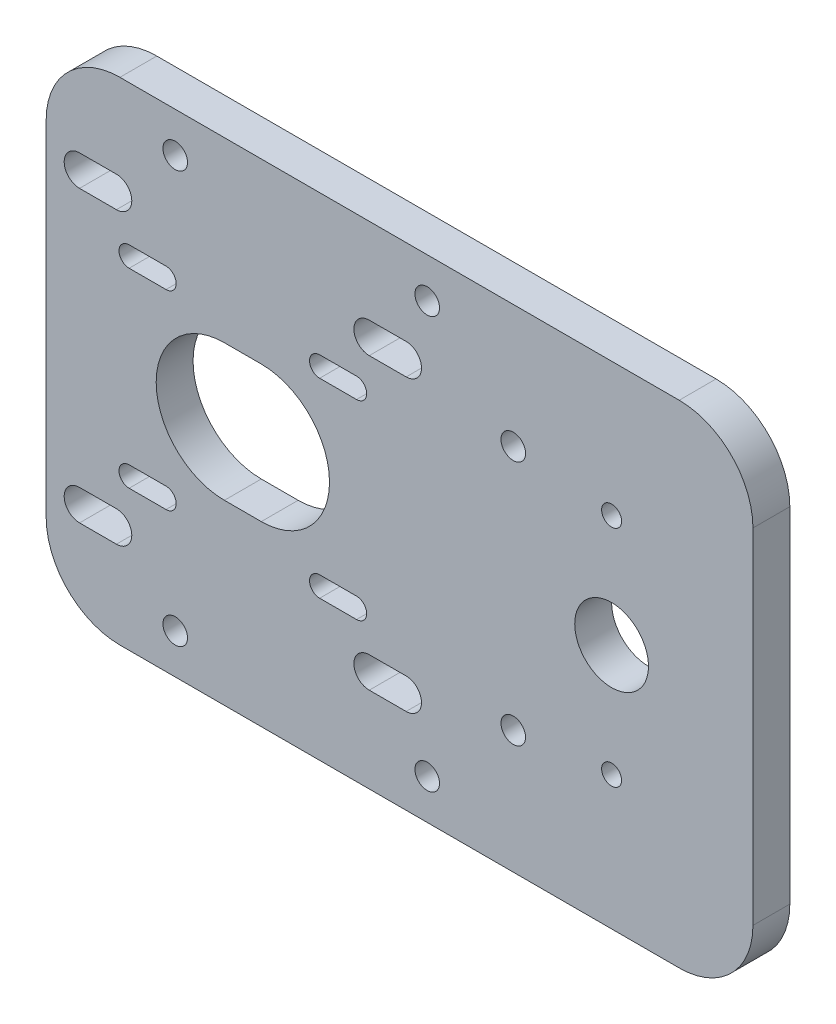
SolidWorks part; units mm, degrees
ref_plane "Alzado" through (0, 0, 0) normal (0, 0, 1) x (1, 0, 0)
ref_plane "Planta" through (0, 0, 0) normal (0, 1, 0) x (1, 0, 0)
ref_plane "Vista lateral" through (0, 0, 0) normal (1, 0, 0) x (0, 0, -1)
sketch "Croquis1" plane through (0, 0, 0) normal (0, 0, 1) x (1, 0, 0)
  line L1 (0, 0) -> (115, 0)
  line L2 (0, 0) -> (0, 80)
  line L3 (0, 80) -> (115, 80)
  line L4 (115, 0) -> (115, 80)
  dimension "D1" = 80
  dimension "D2" = 115
extrude "Saliente-Extruir1" add sketch "Croquis1" along normal blind 6
sketch "Croquis2" plane through (0, 0, 0) normal (0, 0, -1) x (-1, 0, 0)
  line L0 (0, 80) -> (0, 0) construction
  line L1 (0, 40) -> (-115, 40) construction
  line L4 (-115, 0) -> (-115, 80) construction
  line L7 (-29, 40) -> (-35, 40) construction
  line L10 (-29, 28.9) -> (-35, 28.9)
  line L19 (-29, 51.1) -> (-35, 51.1)
  line L20 (-13.5, 24.5) -> (-19.5, 24.5) construction
  line L21 (-13.5, 22.85) -> (-19.5, 22.85)
  line L22 (-13.5, 26.15) -> (-19.5, 26.15)
  line L23 (-44.5, 55.5) -> (-50.5, 55.5) construction
  line L24 (-44.5, 53.85) -> (-50.5, 53.85)
  line L25 (-44.5, 57.15) -> (-50.5, 57.15)
  line L26 (-44.5, 24.5) -> (-50.5, 24.5) construction
  line L27 (-44.5, 22.85) -> (-50.5, 22.85)
  line L28 (-44.5, 26.15) -> (-50.5, 26.15)
  line L29 (-13.5, 55.5) -> (-19.5, 55.5) construction
  line L30 (-13.5, 53.85) -> (-19.5, 53.85)
  line L31 (-13.5, 57.15) -> (-19.5, 57.15)
  line L32 (-92, 0) -> (-92, 80) construction
  line L33 (0, 0) -> (-115, 0) construction
  line L34 (-115, 80) -> (0, 80) construction
  line L35 (-61, 0) -> (-61, 80) construction
  line L36 (-52.57, 16.43) -> (-58.57, 16.43) construction
  line L37 (-52.57, 13.93) -> (-58.57, 13.93)
  line L38 (-52.57, 18.93) -> (-58.57, 18.93)
  line L39 (-5.43, 16.43) -> (-11.43, 16.43) construction
  line L40 (-5.43, 13.93) -> (-11.43, 13.93)
  line L41 (-5.43, 18.93) -> (-11.43, 18.93)
  line L42 (-52.57, 63.57) -> (-58.57, 63.57) construction
  line L43 (-52.57, 61.07) -> (-58.57, 61.07)
  line L44 (-52.57, 66.07) -> (-58.57, 66.07)
  line L45 (-5.43, 63.57) -> (-11.43, 63.57) construction
  line L46 (-5.43, 61.07) -> (-11.43, 61.07)
  line L47 (-5.43, 66.07) -> (-11.43, 66.07)
  circle A5 centre (-92, 40) radius 6
  circle A15 centre (-92, 21.75) radius 1.625
  circle A16 centre (-92, 58.25) radius 1.625
  arc A19 (-29, 28.9) -> (-29, 51.1) centre (-29, 40) ccw
  arc A20 (-35, 51.1) -> (-35, 28.9) centre (-35, 40) ccw
  arc A21 (-13.5, 22.85) -> (-13.5, 26.15) centre (-13.5, 24.5) ccw
  arc A22 (-19.5, 26.15) -> (-19.5, 22.85) centre (-19.5, 24.5) ccw
  arc A23 (-44.5, 53.85) -> (-44.5, 57.15) centre (-44.5, 55.5) ccw
  arc A24 (-50.5, 57.15) -> (-50.5, 53.85) centre (-50.5, 55.5) ccw
  arc A25 (-44.5, 22.85) -> (-44.5, 26.15) centre (-44.5, 24.5) ccw
  arc A26 (-50.5, 26.15) -> (-50.5, 22.85) centre (-50.5, 24.5) ccw
  arc A27 (-13.5, 53.85) -> (-13.5, 57.15) centre (-13.5, 55.5) ccw
  arc A28 (-19.5, 57.15) -> (-19.5, 53.85) centre (-19.5, 55.5) ccw
  arc A29 (-52.57, 13.93) -> (-52.57, 18.93) centre (-52.57, 16.43) ccw
  arc A30 (-58.57, 18.93) -> (-58.57, 13.93) centre (-58.57, 16.43) ccw
  arc A31 (-5.43, 13.93) -> (-5.43, 18.93) centre (-5.43, 16.43) ccw
  arc A32 (-11.43, 18.93) -> (-11.43, 13.93) centre (-11.43, 16.43) ccw
  arc A33 (-52.57, 61.07) -> (-52.57, 66.07) centre (-52.57, 63.57) ccw
  arc A34 (-58.57, 66.07) -> (-58.57, 61.07) centre (-58.57, 63.57) ccw
  arc A35 (-5.43, 61.07) -> (-5.43, 66.07) centre (-5.43, 63.57) ccw
  arc A36 (-11.43, 66.07) -> (-11.43, 61.07) centre (-11.43, 63.57) ccw
  circle A37 centre (-76, 20) radius 2
  circle A38 centre (-76, 60) radius 2
  point P6 (-32, 40)
  point P19 (-16.5, 24.5)
  point P28 (-47.5, 55.5)
  point P35 (-47.5, 24.5)
  point P41 (-55.57, 16.43)
  point P48 (-16.5, 55.5)
  point P63 (-8.43, 16.43)
  point P72 (-55.57, 63.57)
  point P79 (-8.43, 63.57)
  dimension "D2" = 6
  dimension "D3" = 11.1
  dimension "D4" = 3.3
  dimension "D5" = 6
  dimension "D6" = 12
  dimension "D13" = 3.25
  dimension "D14" = 3.25
  dimension "D29" = 2.5
  dimension "D32" = 2.5
  dimension "D34" = 2.5
  dimension "D36" = 2.5
  dimension "D45" = 4
  dimension "D46" = 4
  dimension "D7" = 15.5
  dimension "D8" = 15.5
  dimension "D9" = 3.3
  dimension "D10" = 6
  dimension "D11" = 23
  dimension "D12" = 40
  dimension "D15" = 18.25
  dimension "D16" = 18.25
  dimension "D17" = 3.3
  dimension "D18" = 6
  dimension "D19" = 3.3
  dimension "D20" = 6
  dimension "D21" = 15.5
  dimension "D22" = 15.5
  dimension "D23" = 15.5
  dimension "D24" = 15.5
  dimension "D25" = 15.5
  dimension "D26" = 15.5
  dimension "D27" = 60
  dimension "D28" = 26
  dimension "D30" = 6
  dimension "D31" = 6
  dimension "D33" = 6
  dimension "D35" = 6
  dimension "D37" = 23.57
  dimension "D38" = 23.57
  dimension "D39" = 23.57
  dimension "D40" = 23.57
  dimension "D41" = 23.57
  dimension "D42" = 23.57
  dimension "D43" = 23.57
  dimension "D44" = 23.57
  dimension "D47" = 20
  dimension "D48" = 39
  dimension "D49" = 39
  dimension "D50" = 20
extrude "Cortar-Extruir1" cut sketch "Croquis2" against normal through all
fillet "Redondeo1" radius 12 4 edges at (115, 0, 3) (115, 80, 3) (0, 0, 3) (0, 80, 3)
sketch "Croquis3" plane through (0, 0, 0) normal (0, 0, -1) x (-1, 0, 0)
  line L0 (-12, 0) -> (-103, 0) construction
  line L1 (0, 68) -> (0, 12) construction
  line L2 (-103, 80) -> (-12, 80) construction
  circle A0 centre (-21, 6.5) radius 2
  circle A1 centre (-62, 6.5) radius 2
  circle A2 centre (-62, 73.5) radius 2
  circle A3 centre (-21, 73.5) radius 2
  dimension "D1" = 4
  dimension "D2" = 4
  dimension "D3" = 4
  dimension "D4" = 4
  dimension "D5" = 6.5
  dimension "D6" = 6.5
  dimension "D7" = 21
  dimension "D8" = 62
  dimension "D9" = 6.5
  dimension "D10" = 6.5
  dimension "D11" = 21
  dimension "D12" = 62
extrude "Cortar-Extruir2" cut sketch "Croquis3" against normal through all
